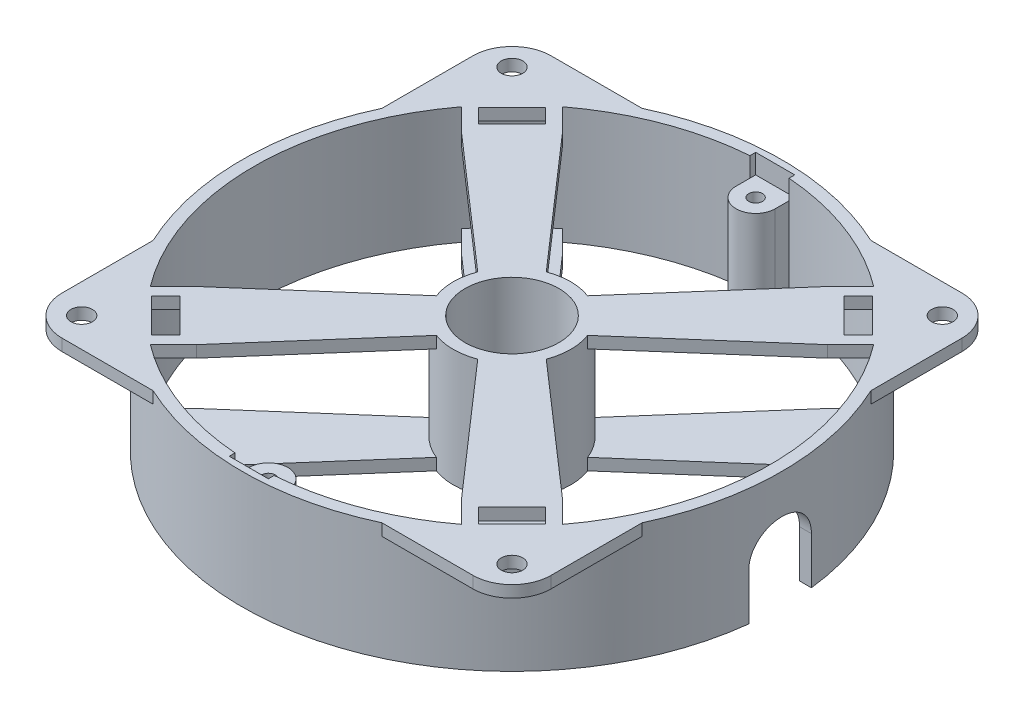
SolidWorks part; units mm, degrees
note: The reader was unsure of these and kept them because the rebuilt part matched: shared geometry of "Sketch12<3>".
ref_plane "Front Plane" through (0, 0, 0) normal (0, 0, 1) x (1, 0, 0)
ref_plane "Top Plane" through (0, 0, 0) normal (0, 1, 0) x (1, 0, 0)
ref_plane "Right Plane" through (0, 0, 0) normal (1, 0, 0) x (0, 0, -1)
sketch "Sketch1" plane through (0, 0, 0) normal (0, 1, 0) x (1, 0, 0)
  circle A0 centre (0, 0) radius 69
  dimension "D1" = 138
extrude "Boss-Extrude1" add sketch "Sketch1" along normal blind 30
sketch "Sketch2" plane through (0, 30, 0) normal (0, 1, 0) x (1, 0, 0)
  line L1 (62.5, -62.5) -> (-62.5, -62.5)
  line L2 (62.5, -62.5) -> (62.5, 62.5)
  line L3 (62.5, 62.5) -> (-62.5, 62.5)
  line L4 (-62.5, -62.5) -> (-62.5, 62.5)
  line L5 (62.5, -62.5) -> (-62.5, 62.5) construction
  line L6 (62.5, 62.5) -> (-62.5, -62.5) construction
  point P0 (0, 0)
  dimension "D1" = 125
  dimension "D2" = 125
extrude "Boss-Extrude2" add sketch "Sketch2" against normal blind 3
sketch "Sketch3" plane through (0, 30, 0) normal (0, 1, 0) x (1, 0, 0)
  line L1 (55, -55) -> (-55, -55) construction
  line L2 (55, -55) -> (55, 55) construction
  line L3 (55, 55) -> (-55, 55) construction
  line L4 (-55, -55) -> (-55, 55) construction
  line L5 (55, -55) -> (-55, 55) construction
  line L6 (55, 55) -> (-55, -55) construction
  circle A0 centre (55, 55) radius 2.75
  circle A1 centre (-55, 55) radius 2.75
  circle A2 centre (-55, -55) radius 2.75
  circle A3 centre (55, -55) radius 2.75
  point P0 (0, 0)
  dimension "D3" = 5.5
  dimension "D1" = 110
  dimension "D2" = 110
extrude "Cut-Extrude1" cut sketch "Sketch3" against normal blind 3
sketch "Sketch4" plane through (0, 0, 0) normal (0, -1, 0) x (1, 0, 0)
  circle A0 centre (0, 0) radius 66
  circle A1 centre (0, 0) radius 69 construction
  dimension "D1" = 3
extrude "Cut-Extrude2" cut sketch "Sketch4" against normal through all
fillet "Fillet1" radius 10 4 edges at (-62.5, 28.5, -62.5) (-62.5, 28.5, 62.5) (62.5, 28.5, 62.5) (62.5, 28.5, -62.5)
sketch "Sketch5" plane through (0, 30, 0) normal (0, 1, 0) x (1, 0, 0)
  line L0 (-55, 55) -> (55, -55) construction
  line L1 (-55, -55) -> (55, 55) construction
sketch "Sketch6" plane through (0, 0, 0) normal (1, 0, 0) x (0, 0, -1)
  line L0 (0, 0) -> (0, 12) construction
  line L1 (-8, 0) -> (-8, 12)
  line L2 (8, 0) -> (8, 12)
  arc A0 (-8, 0) -> (8, 0) centre (0, 0) ccw
  arc A1 (8, 12) -> (-8, 12) centre (0, 12) ccw
  point P3 (0, 6)
  dimension "D1" = 16
  dimension "D2" = 12
extrude "Cut-Extrude3" cut sketch "Sketch6" along normal through all
sketch "Sketch8" plane through (0, 30, 0) normal (0, 1, 0) x (1, 0, 0)
  line L0 (41.79, 50.4167) -> (50.4167, 41.79)
  line L1 (41.79, 50.4167) -> (38.1131, 46.7398)
  line L2 (50.4167, 41.79) -> (46.7398, 38.1131)
  line L3 (38.1131, 46.7398) -> (46.7398, 38.1131)
  line L4 (-55, -55) -> (55, 55) construction
  line L5 (41.79, 54.6594) -> (33.8704, 46.7398)
  line L6 (33.8704, 46.7398) -> (46.7398, 33.8704)
  line L7 (54.6594, 41.79) -> (46.7398, 33.8704)
  line L8 (41.79, 54.6594) -> (54.6594, 41.79)
  dimension "D1" = 5.2
  dimension "D2" = 12.2
  dimension "D3" = 6.1
  dimension "D4" = 60
  dimension "D5" = 3
extrude "Boss-Extrude4" add sketch "Sketch8" against normal up to surface (30 mm away) up to face at (-0.238, 0, 0)
pattern_circular "CirPattern2" count 4 over 360 about axis through (0, 0, 0) along (0, 1, 0) of "Boss-Extrude4"
sketch "Sketch9" plane through (0, 30, 0) normal (0, 1, 0) x (1, 0, 0)
  line L0 (33.8704, 46.7398) -> (0, 8)
  line L1 (46.7398, 33.8704) -> (8, 0)
  line L2 (-33.8704, 46.7398) -> (0, 8)
  line L3 (-46.7398, 33.8704) -> (-8, 0)
  line L4 (-8, 0) -> (-46.7398, -33.8704)
  line L5 (-33.8704, -46.7398) -> (-46.7398, -33.8704) construction
  line L6 (0, -8) -> (-33.8704, -46.7398)
  line L7 (0, -8) -> (33.8704, -46.7398)
  line L8 (46.7398, -33.8704) -> (33.8704, -46.7398) construction
  line L9 (8, 0) -> (46.7398, -33.8704)
  line L10 (-46.7398, 33.8704) -> (-33.8704, 46.7398)
  line L11 (33.8704, 46.7398) -> (46.7398, 33.8704)
  line L12 (46.7398, -33.8704) -> (33.8704, -46.7398)
  line L13 (-46.7398, -33.8704) -> (-33.8704, -46.7398)
  circle A0 centre (0, 0) radius 8
  dimension "D1" = 16
extrude "Boss-Extrude5" add sketch "Sketch9" along a picked direction on the side against the normal blind 30 contours A0 L2 L10 L3 | A0 L1 L11 L0 | A0 | A0 L4 L13 L6 | A0 L7 L12 L9
ref_plane "Plane1" through (0, 15, 0) normal (0, 1, 0) x (1, 0, 0)
sketch "Sketch10" plane through (0, 15, 0) normal (0, 1, 0) x (1, 0, 0)
  circle A0 centre (0, 0) radius 66
  dimension "D1" = 132
extrude "Cut-Extrude4" cut sketch "Sketch10" against normal blind 12 and the other way blind 12
sketch "Sketch11" plane through (0, 0, 0) normal (0, -1, 0) x (1, 0, 0)
  circle A0 centre (0, 0) radius 15
extrude "Boss-Extrude6" add sketch "Sketch11" against normal blind 30
sketch "Sketch12" plane through (0, 0, 0) normal (0, -1, 0) x (1, 0, 0)
  line L0 (5, 62.2785) -> (5, 67.2785)
  line L1 (5, 67.2785) -> (-5, 67.2785)
  line L2 (-5, 67.2785) -> (-5, 62.2785)
  circle A0 centre (0, 62.2785) radius 1.75
  arc A1 (-5, 62.2785) -> (5, 62.2785) centre (0, 62.2785) ccw
  dimension "D1" = 3.5
  dimension "D2" = 10
extrude "Boss-Extrude9" add sketch "Sketch12" against normal blind 30
mirror "Mirror1" about plane through (0, 0, 0) normal (0, 0, 1) of "Boss-Extrude9"
extrude "Cut-Extrude5" cut sketch "Sketch12<3>" along normal blind 5 from surface at -30 starting at face at (0, 30, -48.4015)
sketch "Sketch12<3>" plane through (0, 0, 0) normal (0, -1, 0) x (1, 0, 0) same geometry as "Sketch12"
mirror "Mirror2" about plane through (0, 0, 0) normal (0, 0, 1) of "Cut-Extrude5"
sketch "Sketch14" plane through (0, 30, 0) normal (0, 1, 0) x (1, 0, 0)
  circle A0 centre (0, 0) radius 12
  dimension "D1" = 24
extrude "Cut-Extrude6" cut sketch "Sketch14" against normal through all
